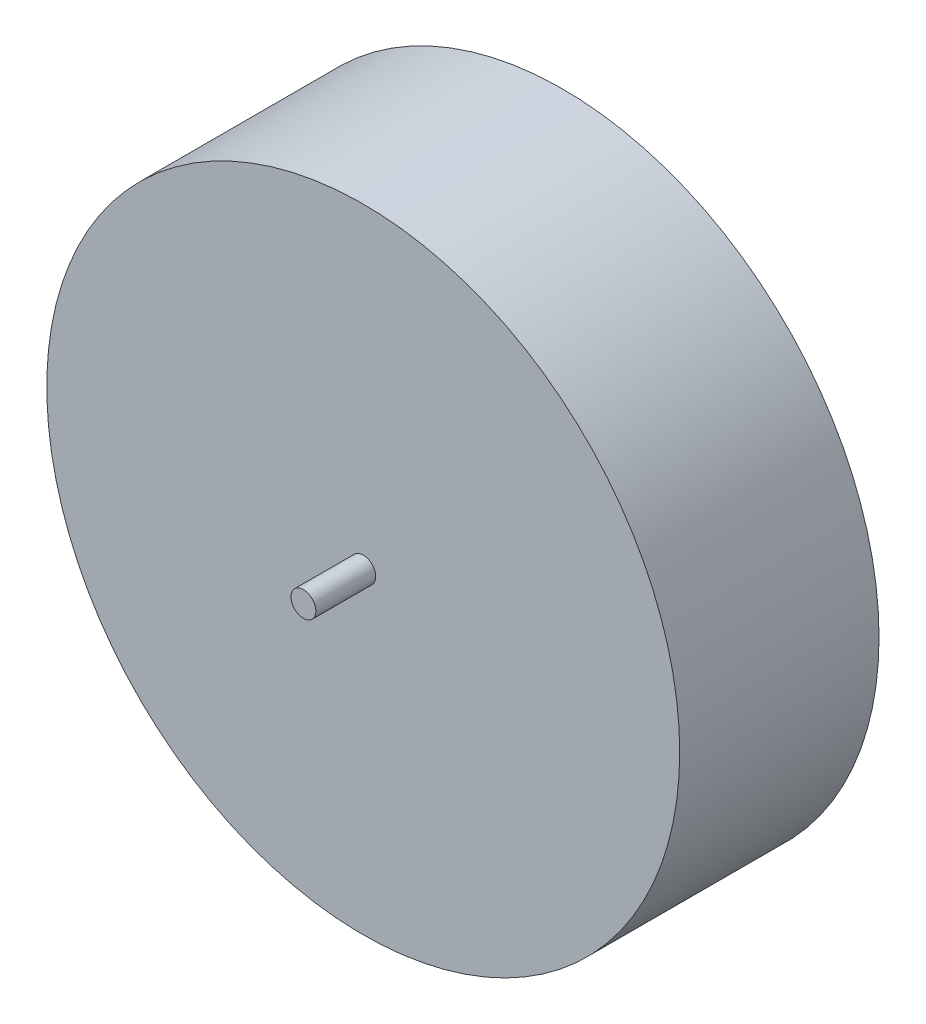
SolidWorks part; units mm, degrees
ref_plane "Front Plane" through (0, 0, 0) normal (0, 0, 1) x (1, 0, 0)
ref_plane "Top Plane" through (0, 0, 0) normal (0, 1, 0) x (1, 0, 0)
ref_plane "Right Plane" through (0, 0, 0) normal (1, 0, 0) x (0, 0, -1)
sketch "Sketch1" plane through (0, 0, 0) normal (0, 0, 1) x (1, 0, 0)
  circle A0 centre (0, 0) radius 190.5
  dimension "D1" = 381
extrude "Boss-Extrude1" add sketch "Sketch1" along normal mid plane 120
sketch "Sketch2" plane through (0, 0, 0) normal (0, 0, 1) x (1, 0, 0)
  circle A0 centre (0, 0) radius 7.5
  dimension "D1" = 15
extrude "Boss-Extrude2" add sketch "Sketch2" along normal mid plane 192
